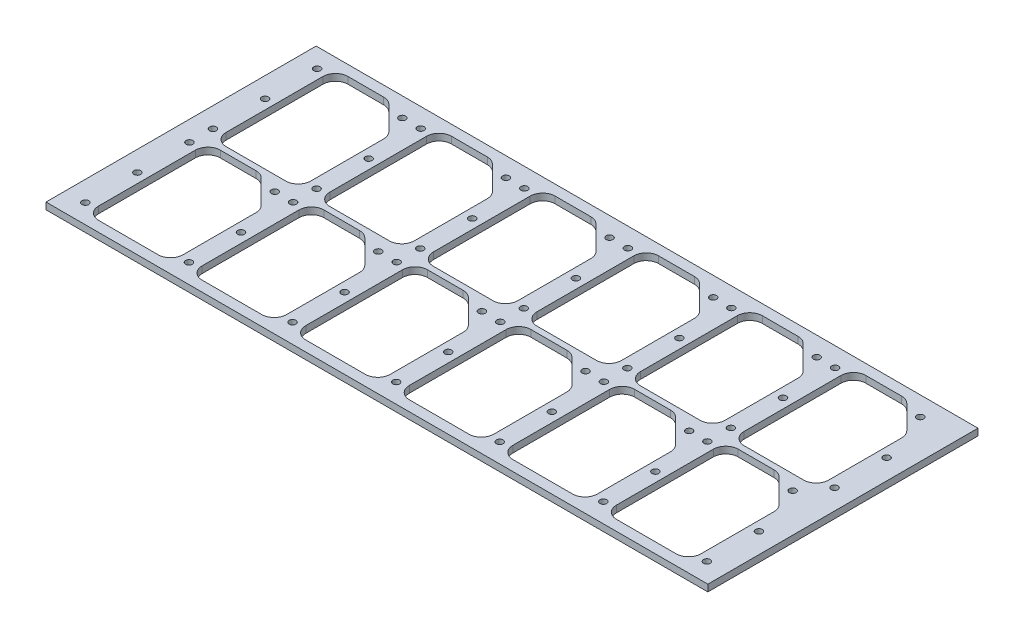
SolidWorks part; units mm, degrees
ref_plane "Front Plane" through (0, 0, 0) normal (0, 0, 1) x (1, 0, 0)
ref_plane "Top Plane" through (0, 0, 0) normal (0, 1, 0) x (1, 0, 0)
ref_plane "Right Plane" through (0, 0, 0) normal (1, 0, 0) x (0, 0, -1)
sketch "Sketch1" plane through (0, 0, 0) normal (0, 1, 0) x (1, 0, 0)
  line L1 (-311.15, -127) -> (311.15, -127)
  line L2 (-311.15, -127) -> (-311.15, 127)
  line L3 (-311.15, 127) -> (311.15, 127)
  line L4 (311.15, -127) -> (311.15, 127)
  line L5 (-311.15, -127) -> (311.15, 127) construction
  line L6 (-311.15, 127) -> (311.15, -127) construction
  point P0 (0, 0)
  dimension "D1" = 254
  dimension "D2" = 622.3
extrude "Boss-Extrude1" add sketch "Sketch1" along normal blind 6.35
sketch "Sketch2" plane through (0, 6.35, 0) normal (0, 1, 0) x (1, 0, 0)
  line L15 (-277.2, -99.5) -> (-277.2, -105.5) construction
  line L16 (-209.8, -105.5) -> (-209.8, -99.5) construction
  line L17 (-271.5, -111.2) -> (-215.5, -111.2) construction
  line L18 (-237.864, -8.8) -> (-271.5, -8.8) construction
  line L19 (-211.4695, -32.8335) -> (-233.8335, -10.4695) construction
  line L20 (-207.2269, -28.5908) -> (-229.5908, -6.2269)
  line L21 (-237.864, -2.8) -> (-271.5, -2.8)
  line L22 (-283.2, -14.5) -> (-283.2, -105.5)
  line L23 (-271.5, -117.2) -> (-215.5, -117.2)
  line L24 (-203.8, -105.5) -> (-203.8, -36.864)
  arc A15 (-233.8335, -10.4695) -> (-237.864, -8.8) centre (-237.864, -14.5) ccw construction
  arc A16 (-271.5, -8.8) -> (-277.2, -14.5) centre (-271.5, -14.5) ccw construction
  arc A17 (-209.8, -36.864) -> (-211.4695, -32.8335) centre (-215.5, -36.864) ccw construction
  arc A18 (-277.2, -105.5) -> (-271.5, -111.2) centre (-271.5, -105.5) ccw construction
  arc A19 (-215.5, -111.2) -> (-209.8, -105.5) centre (-215.5, -105.5) ccw construction
  arc A20 (-203.8, -36.864) -> (-207.2269, -28.5908) centre (-215.5, -36.864) ccw
  arc A21 (-229.5908, -6.2269) -> (-237.864, -2.8) centre (-237.864, -14.5) ccw
  arc A22 (-271.5, -2.8) -> (-283.2, -14.5) centre (-271.5, -14.5) ccw
  arc A23 (-283.2, -105.5) -> (-271.5, -117.2) centre (-271.5, -105.5) ccw
  arc A24 (-215.5, -117.2) -> (-203.8, -105.5) centre (-215.5, -105.5) ccw
  dimension "D6" = 6
  dimension "D7" = 6
  dimension "D8" = 6
  dimension "D9" = 6
  dimension "D10" = 6
  dimension "D1" = 6
  dimension "D2" = 6
  dimension "D3" = 6
  dimension "D4" = 6
  dimension "D5" = 6
extrude "Cut-Extrude1" cut sketch "Sketch2" against normal through all
pattern_linear "LPattern1" count 6 spacing 97.4 along (1, 0, 0) count 2 spacing 120 along (0, 0, -1) of "Cut-Extrude1"
sketch "Sketch3" plane through (0, 6.35, 0) normal (0, 1, 0) x (1, 0, 0)
  line L0 (-292.2, 60) -> (-292.2, 108.9551) construction
  line L1 (-292.2, 11.0449) -> (-292.2, 60) construction
  line L2 (-194.8, 11.0449) -> (-194.8, 60) construction
  line L3 (-194.8, 60) -> (-194.8, 108.9551) construction
  line L4 (-194.8, 108.9551) -> (-212.0449, 108.9551) construction
  line L5 (-243.5, 2.8) -> (-243.5, 60) construction
  line L6 (-271.5, 2.8) -> (-215.5, 2.8) construction
  line L7 (-243.5, 60) -> (-283.2, 60) construction
  line L8 (-283.2, 105.5) -> (-283.2, 14.5) construction
  line L9 (-292.2, 60) -> (-194.8, 60) construction
  line L10 (-218.4088, 102.5912) -> (-212.0449, 108.9551) construction
  line L11 (-207.2269, 91.4092) -> (-229.5908, 113.7731) construction
  line L12 (-203.8, 43.0325) -> (-185.8, 43.0325) construction
  line L13 (-203.8, 14.5) -> (-203.8, 83.136) construction
  line L14 (-185.8, 105.5) -> (-185.8, 14.5) construction
  line L15 (-194.8, 72.9185) -> (-203.8, 72.9185) construction
  circle A0 centre (-292.2, 108.9551) radius 3.175
  circle A1 centre (-292.2, 11.0449) radius 3.175
  circle A2 centre (-212.0449, 108.9551) radius 3.175
  circle A3 centre (-292.2, 60) radius 3.175
  circle A4 centre (-194.8, 60) radius 3.175
  circle A5 centre (-194.8, 11.0449) radius 3.175
  point P17 (-243.5, 60)
  point P30 (-194.8, 43.0325)
  dimension "D1" = 6.35
  dimension "D3" = 90
extrude "Cut-Extrude2" cut sketch "Sketch3" against normal through all
pattern_linear "LPattern2" count 6 spacing 97.4 along (1, 0, 0) count 2 spacing 120 along (0, 0, 1) of "Cut-Extrude2"
sketch "Sketch4" plane through (0, 6.35, 0) normal (0, 1, 0) x (1, 0, 0)
  point P0 (0, 0)
sketch "Sketch5" plane through (0, 0, 0) normal (0, -1, 0) x (1, 0, 0)
  point P0 (0, 0)
